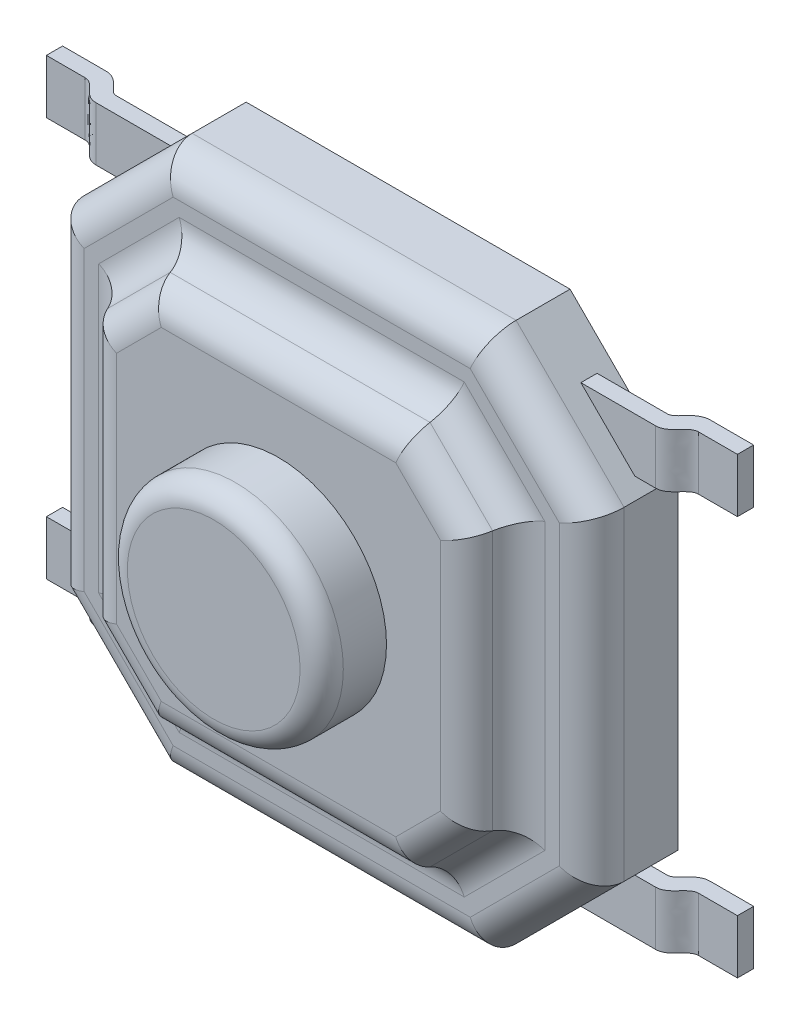
SolidWorks part; units mm, degrees
ref_plane "Front Plane" through (0, 0, 0) normal (0, 0, 1) x (1, 0, 0)
ref_plane "Top Plane" through (0, 0, 0) normal (0, 1, 0) x (1, 0, 0)
ref_plane "Right Plane" through (0, 0, 0) normal (1, 0, 0) x (0, 0, -1)
sketch "Sketch1" plane through (0, 0, 0) normal (0, 0, 1) x (1, 0, 0)
  line L0 (0, 0) -> (0, 2.5) construction
  line L1 (0, 0) -> (2.5, 0) construction
  line L2 (-1.5, 2.5) -> (1.5, 2.5)
  line L3 (1.5, 2.5) -> (2.5, 1.5)
  line L4 (2.5, 1.5) -> (2.5, -1.5)
  line L5 (1.5, -2.5) -> (2.5, -1.5)
  line L6 (-1.5, -2.5) -> (1.5, -2.5)
  line L7 (-1.5, -2.5) -> (-2.5, -1.5)
  line L8 (-2.5, 1.5) -> (-2.5, -1.5)
  line L9 (-1.5, 2.5) -> (-2.5, 1.5)
  point P13 (0, -2.5)
  dimension "D1" = 45
  dimension "D2" = 2.5
  dimension "D3" = 1.5
extrude "Boss-Extrude1" add sketch "Sketch1" along normal blind 0.8
sketch "Sketch2" plane through (0, 0, 0.8) normal (0, 0, 1) x (1, 0, 0)
  line L46 (-1.2101, 1.8) -> (-1.8, 1.2101)
  line L47 (-1.8, 1.2101) -> (-1.8, -1.2101)
  line L48 (-1.8, -1.2101) -> (-1.2101, -1.8)
  line L49 (-1.2101, -1.8) -> (1.2101, -1.8)
  line L50 (1.2101, -1.8) -> (1.8, -1.2101)
  line L51 (1.8, -1.2101) -> (1.8, 1.2101)
  line L52 (1.8, 1.2101) -> (1.2101, 1.8)
  line L53 (1.2101, 1.8) -> (-1.2101, 1.8)
  line L54 (-1.2101, 1.8) -> (-1.8, 1.2101)
  line L55 (-1.8, 1.2101) -> (-1.8, -1.2101)
  line L56 (-1.8, -1.2101) -> (-1.2101, -1.8)
  line L57 (-1.2101, -1.8) -> (1.2101, -1.8)
  line L58 (1.2101, -1.8) -> (1.8, -1.2101)
  line L59 (1.8, -1.2101) -> (1.8, 1.2101)
  line L60 (1.8, 1.2101) -> (1.2101, 1.8)
  line L61 (1.2101, 1.8) -> (-1.2101, 1.8)
  dimension "D1" = 0.7
extrude "Boss-Extrude2" add sketch "Sketch2" along normal offset from surface (0.4 mm away) 1.2 up to face at (0, 0, 0)
sketch "Sketch3" plane through (0, 0, 1.2) normal (0, 0, 1) x (1, 0, 0)
  circle A0 centre (0, 0) radius 1
  dimension "D1" = 2
extrude "Boss-Extrude3" add sketch "Sketch3" along normal offset from surface (0.6 mm away) 1.8 up to face at (0, 0, 0)
fillet "Fillet1" radius 0.3 8 edges at (-1.505, 1.505, 1.2) (0, 1.8, 1.2) (1.505, 1.505, 1.2) (1.8, 0, 1.2) (1.505, -1.505, 1.2) (0, -1.8, 1.2) (-1.505, -1.505, 1.2) (-1.8, 0, 1.2)
fillet "Fillet2" radius 0.3 8 edges at (-2, -2, 0.8) (0, -2.5, 0.8) (2, -2, 0.8) (2.5, 0, 0.8) (2, 2, 0.8) (0, 2.5, 0.8) (-2, 2, 0.8) (-2.5, 0, 0.8)
ref_plane "Plane1" through (0, 1.85, 0) normal (0, 1, 0) x (1, 0, 0)
fillet "Fillet3" radius 0.3 8 edges at (0, -1.8, 0.8) (1.505, -1.505, 0.8) (1.8, 0, 0.8) (1.505, 1.505, 0.8) (0, 1.8, 0.8) (-1.505, 1.505, 0.8) (-1.8, 0, 0.8) (-1.505, -1.505, 0.8)
fillet "Fillet4" radius 0.2 1 edges at (1, 0, 1.8)
sketch "Sketch4" plane through (0, 1.85, 0) normal (0, 1, 0) x (1, 0, 0)
  line L0 (0, -0.15) -> (-2.55, -0.15)
  line L1 (-3.2, 0) -> (-2.8, 0)
  line L2 (1.5, 0) -> (-1.5, 0) construction
  line L3 (0, 0) -> (0, -0.15) construction
  line L5 (-2.5, -0.5) -> (-2.5, 0) construction
  line L6 (-3.2, -0.15) -> (-2.8415, -0.15)
  line L7 (0, -0.3) -> (-2.5915, -0.3)
  line L8 (-3.2, 0) -> (-3.2, -0.15)
  line L9 (-2.8, 0) -> (-2.55, -0.15) construction
  line L10 (-2.8415, -0.15) -> (-2.5915, -0.3) construction
  line L11 (0, -0.15) -> (2.55, -0.15)
  line L12 (3.2, 0) -> (2.8, 0)
  line L13 (3.2, 0) -> (3.2, -0.15)
  line L14 (3.2, -0.15) -> (2.8415, -0.15)
  line L15 (0, -0.3) -> (2.5915, -0.3)
  spline S0 degree 3 poles (-2.8, 0) (-2.6624, 0) (-2.6305, -0.15) (-2.55, -0.15) knots 0 0 0 0 1 1 1 1
  spline S1 degree 3 poles (-2.5915, -0.3) (-2.7133, -0.3) (-2.7444, -0.15) (-2.8415, -0.15) knots 0 0 0 0 1 1 1 1
  spline S2 degree 3 poles (2.8, 0) (2.6624, 0) (2.6305, -0.15) (2.55, -0.15) knots 0 0 0 0 1 1 1 1
  spline S3 degree 3 poles (2.5915, -0.3) (2.7133, -0.3) (2.7444, -0.15) (2.8415, -0.15) knots 0 0 0 0 1 1 1 1
  dimension "D1" = 3.2
  dimension "D2" = 0.4
  dimension "D3" = 0.15
  dimension "D4" = 0.05
  dimension "D5" = 0.15
extrude "Boss-Extrude4" add sketch "Sketch4" along normal mid plane 0.5
mirror "Mirror1" about plane through (0, 0, 0) normal (0, 1, 0) of "Boss-Extrude4"
ref_axis "Axis1" through (0, 0, -0.075) along (0, 0, 1)
